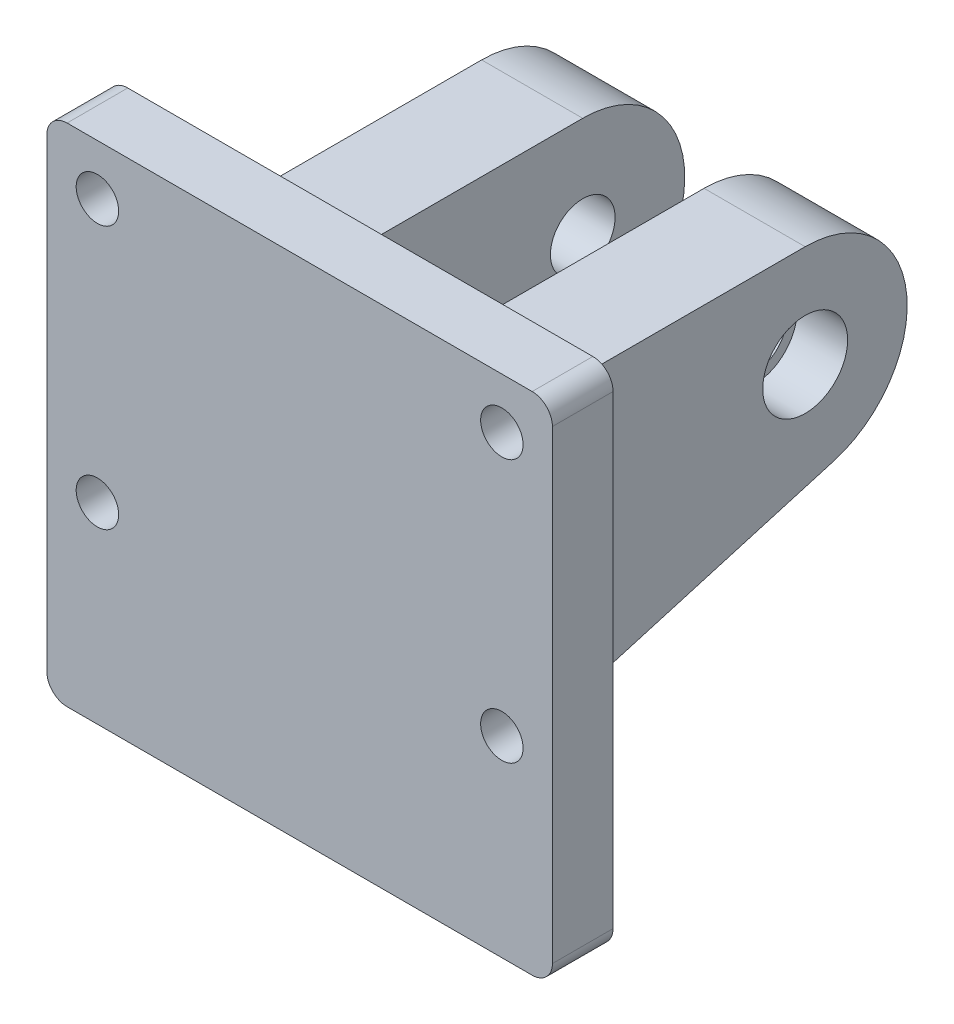
SolidWorks part; units mm, degrees
material "ABS"
ref_plane "Front Plane" through (0, 0, 0) normal (0, 0, 1) x (1, 0, 0)
ref_plane "Top Plane" through (0, 0, 0) normal (0, 1, 0) x (1, 0, 0)
ref_plane "Right Plane" through (0, 0, 0) normal (1, 0, 0) x (0, 0, -1)
sketch "Sketch1" plane through (0, 0, 0) normal (0, 0, 1) x (1, 0, 0)
  line L1 (-12.5, 12.5) -> (12.5, 12.5)
  line L2 (-12.5, 12.5) -> (-12.5, -12.5)
  line L3 (-12.5, -12.5) -> (12.5, -12.5)
  line L4 (12.5, 12.5) -> (12.5, -12.5)
  line L5 (-12.5, 12.5) -> (12.5, -12.5) construction
  line L6 (-12.5, -12.5) -> (12.5, 12.5) construction
  point P0 (0, 0)
  dimension "D1" = 25
  dimension "D2" = 25
extrude "Boss-Extrude1" add sketch "Sketch1" along normal blind 3
sketch "Sketch2" plane through (0, 0, 3) normal (0, 0, 1) x (1, 0, 0)
  line L0 (-12.5, 12.5) -> (-12.5, -12.5) construction
  line L1 (12.5, 12.5) -> (-12.5, 12.5) construction
  circle A0 centre (-10, 10) radius 1.05
  dimension "D1" = 2.1
  dimension "D2" = 2.5
  dimension "D3" = 2.5
extrude "Cut-Extrude1" cut sketch "Sketch2" against normal through all
pattern_linear "LPattern1" count 2 spacing 20 along (1, 0, 0) count 2 spacing 13 along (0, -1, 0) of "Cut-Extrude1"
sketch "Sketch3" plane through (0, 0, 0) normal (1, 0, 0) x (0, 0, -1)
  line L0 (0, 8.4526) -> (0, -5.9239)
  line L1 (0, -12.5) -> (0, 12.5) construction
  line L2 (0, -5.9239) -> (15.4107, -1.4355)
  line L3 (0, 8.4526) -> (14, 8.4526)
  arc A0 (15.4107, -1.4355) -> (14, 8.4526) centre (14, 3.4079) ccw
  circle A1 centre (14, 3.4079) radius 1.6
  point P7 (0, 0)
  dimension "D1" = 3.2
  dimension "D2" = 14
extrude "Boss-Extrude2" add sketch "Sketch3" along normal blind 5 from offset 3
mirror "Mirror1" about plane through (0, 0, 0) normal (1, 0, 0) of "Boss-Extrude2"
sketch "Sketch4" plane through (8, 0, 0) normal (1, 0, 0) x (0, 0, -1)
  circle A0 centre (14, 3.4079) radius 2.1
  dimension "D1" = 4.2
extrude "Cut-Extrude2" cut sketch "Sketch4" against normal blind 2.5
fillet "Fillet1" radius 1 8 edges at (12.5, -12.5, 1.5) (12.5, 12.5, 1.5) (-12.5, 12.5, 1.5) (-12.5, -12.5, 1.5) (-8, 1.2643, 0) (3, 1.2643, 0) (-3, 1.2643, 0) (8, 1.2643, 0)
